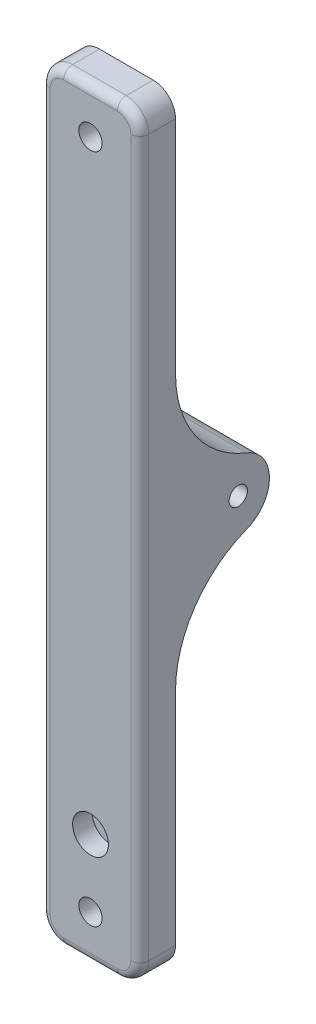
SolidWorks part; units mm, degrees
material "POM Acetal Copolymer"
ref_plane "Front Plane" through (0, 0, 0) normal (0, 0, 1) x (1, 0, 0)
ref_plane "Top Plane" through (0, 0, 0) normal (0, 1, 0) x (1, 0, 0)
ref_plane "Right Plane" through (0, 0, 0) normal (1, 0, 0) x (0, 0, -1)
sketch "Sketch1" plane through (0, 0, 0) normal (0, 0, 1) x (1, 0, 0)
  line L1 (-11, -85) -> (11, -85)
  line L2 (-11, -85) -> (-11, 85)
  line L3 (-11, 85) -> (11, 85)
  line L4 (11, -85) -> (11, 85)
  line L5 (-11, -85) -> (11, 85) construction
  line L6 (-11, 85) -> (11, -85) construction
  point P0 (0, 0)
  dimension "D1" = 22
  dimension "D2" = 170
extrude "Boss-Extrude1" add sketch "Sketch1" along normal mid plane 29
sketch "Sketch2" plane through (11, 0, 0) normal (1, 0, 0) x (0, 0, -1)
  line L0 (-14.5, -85) -> (-14.5, 85) construction
  line L2 (14.5, 85) -> (-6.5, 85)
  line L5 (14.5, 85) -> (14.5, 6)
  line L6 (14.5, 6) -> (-6.5, 6)
  line L7 (-6.5, 85) -> (-6.5, 6)
  line L8 (14.5, 85) -> (-6.5, 6) construction
  line L9 (14.5, 6) -> (-6.5, 85) construction
  point P4 (4, 45.5)
  dimension "D1" = 8
  dimension "D2" = 6
extrude "Cut-Extrude1" cut sketch "Sketch2" against normal through all contours L7 L6 L5 L2
mirror "Mirror1" about plane through (0, 0, 0) normal (0, 1, 0) of "Cut-Extrude1"
fillet "Fillet3" radius 25 2 edges at (0, 6, 6.5) (0, -6, 6.5)
fillet "Fillet1" radius 5 4 edges at (11, -85, 10.5) (-11, -85, 10.5) (-11, 85, 10.5) (11, 85, 10.5)
fillet "Fillet2" radius 2 8 edges at (-9.5355, -83.5355, 14.5) (-11, 0, 14.5) (-9.5355, 83.5355, 14.5) (0, 85, 14.5) (9.5355, 83.5355, 14.5) (11, 0, 14.5) (9.5355, -83.5355, 14.5) (0, -85, 14.5)
fillet "Fillet4" radius 8 2 edges at (0, -6, -14.5) (0, 6, -14.5)
hole_wizard "Tapped Hole for M5x0.8 Helicoil1" positions "Sketch5" profile "Sketch6" tap size "M5x0.8" standard "Helicoil® Metric" end condition through all
sketch "Sketch5" plane through (0, 0, 14.5) normal (0, 0, 1) x (1, 0, 0)
  point P0 (0, 75)
  dimension "D1" = 75
sketch "Sketch6" plane through (0, 75, 14.5) normal (1, 0, 0) x (0, -1, 0)
  line L0 (0, 0) -> (0, 28.9998)
  line L1 (0, 28.9998) -> (2.6, 28.9998)
  line L2 (2.6, 28.9998) -> (2.6, 0)
  line L5 (2.6, 0) -> (0, 0)
  line L11 (0, -6.35) -> (0, 107.95) construction
  dimension "Thru Tap Drill Dia." = 5.2
  dimension "Thru Tap Drill Depth" = 28.9998
cosmetic thread "Hole Thread1" parameters "D1"=8.87, "D2"=6.145
mirror "Mirror2" about plane through (0, 0, 0) normal (0, 1, 0) of "Tapped Hole for M5x0.8 Helicoil1"
hole_wizard "CBORE for M4 Hex Socket Head Cap Screw1" positions "Sketch7" profile "Sketch8" counterbore size "M4" standard "ISO" end condition through all
sketch "Sketch7" plane through (0, 0, 14.5) normal (0, 0, 1) x (1, 0, 0)
  point P0 (0, -60.0028)
sketch "Sketch8" plane through (0, -60.0028, 14.5) normal (1, 0, 0) x (0, -1, 0)
  line L0 (0, 0) -> (0, 28.9998)
  line L1 (0, 28.9998) -> (2.25, 28.9998)
  line L3 (2.25, 28.9998) -> (2.25, 4.4)
  line L4 (2.25, 4.4) -> (4, 4.4)
  line L5 (4, 4.4) -> (4, 0)
  line L7 (4, 0) -> (0, 0)
  line L11 (0, -6.35) -> (0, 107.95) construction
  dimension "Thru Hole Dia." = 4.5
  dimension "Thru Hole Depth" = 28.9998
  dimension "C'Bore Dia." = 8
  dimension "C'Bore Depth" = 4.4
sketch "Sketch9" plane through (11, 0, 0) normal (1, 0, 0) x (0, 0, -1)
  circle A0 centre (7.517, 0) radius 2.05
  point P3 (0, 0)
  point P4 (0, 0)
  point P5 (0, 0)
  point P6 (7.517, 0)
  dimension "D1" = 4.1
extrude "Cut-Extrude2" cut sketch "Sketch9" against normal through all
